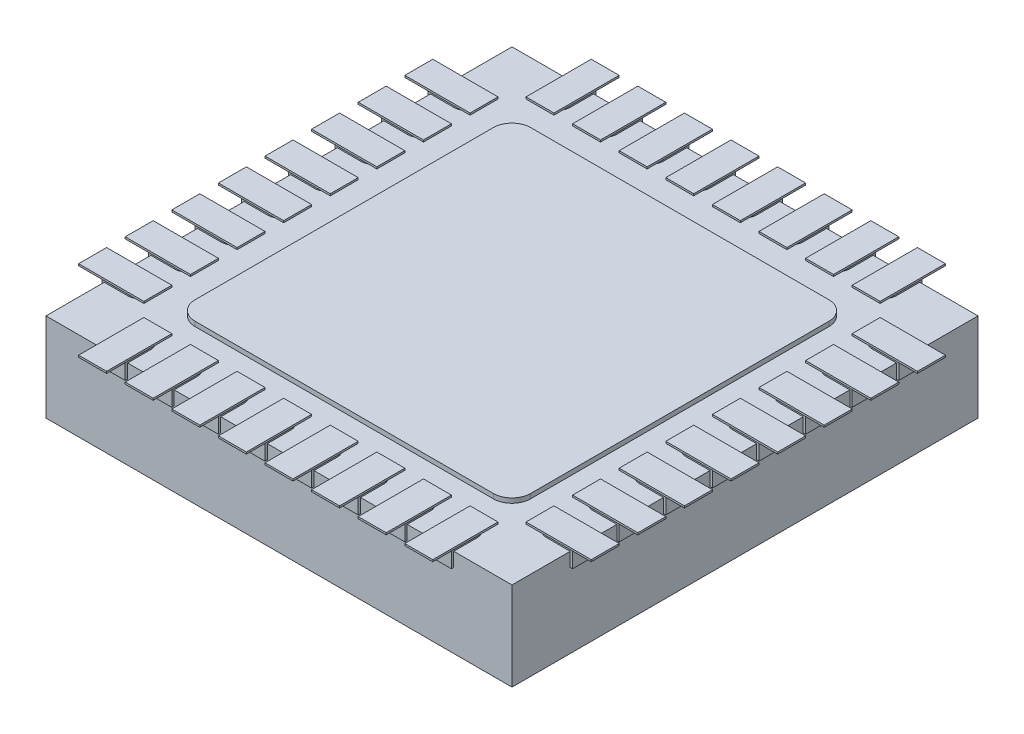
SolidWorks part; units mm, degrees
ref_plane "Front Plane" through (0, 0, 0) normal (0, 0, 1) x (1, 0, 0)
ref_plane "Top Plane" through (0, 0, 0) normal (0, 1, 0) x (1, 0, 0)
ref_plane "Right Plane" through (0, 0, 0) normal (1, 0, 0) x (0, 0, -1)
sketch "Sketch1" plane through (0, 0, 0) normal (0, 1, 0) x (1, 0, 0)
  line L0 (0, -2.75) -> (0, 2.75) construction
  line L1 (-2.525, 2.525) -> (2.525, 2.525)
  line L2 (-2.525, 2.525) -> (-2.525, -2.525)
  line L3 (-2.525, -2.525) -> (2.525, -2.525)
  line L4 (2.525, 2.525) -> (2.525, -2.525)
  line L5 (-2.75, 0) -> (2.75, 0) construction
  dimension "D1" = 5.05
  dimension "D2" = 2.525
  dimension "D3" = 2.525
sketch "Sketch2" plane through (0, 0, 0) normal (0, 1, 0) x (1, 0, 0)
  line L0 (0, -2.75) -> (0, 2.75) construction
  line L1 (-1.6, -1.8) -> (1.6, -1.8)
  line L2 (-1.8, -1.6) -> (-1.8, 1.6)
  line L3 (-1.6, 1.8) -> (1.6, 1.8)
  line L4 (1.8, -1.6) -> (1.8, 1.6)
  line L5 (-2.75, 0) -> (2.75, 0) construction
  line L6 (-1.875, -2.25) -> (-1.875, -2.525)
  line L8 (-1.875, -2.525) -> (-1.625, -2.525)
  line L9 (-1.625, -2.525) -> (-1.625, -2.25)
  line L10 (-1.875, 2.25) -> (-1.875, 2.525)
  line L12 (-1.875, 2.525) -> (-1.625, 2.525)
  line L13 (-1.625, 2.525) -> (-1.625, 2.25)
  line L14 (-1.375, -2.25) -> (-1.375, -2.525)
  line L15 (-1.125, -2.525) -> (-1.125, -2.25)
  line L16 (-1.375, -2.525) -> (-1.125, -2.525)
  line L17 (-1.125, 2.525) -> (-1.125, 2.25)
  line L18 (-1.375, 2.25) -> (-1.375, 2.525)
  line L19 (-1.375, 2.525) -> (-1.125, 2.525)
  line L20 (-0.875, -2.25) -> (-0.875, -2.525)
  line L21 (-0.625, -2.525) -> (-0.625, -2.25)
  line L22 (-0.875, -2.525) -> (-0.625, -2.525)
  line L23 (-0.625, 2.525) -> (-0.625, 2.25)
  line L24 (-0.875, 2.25) -> (-0.875, 2.525)
  line L25 (-0.875, 2.525) -> (-0.625, 2.525)
  line L26 (-0.375, -2.25) -> (-0.375, -2.525)
  line L27 (-0.125, -2.525) -> (-0.125, -2.25)
  line L28 (-0.375, -2.525) -> (-0.125, -2.525)
  line L29 (-0.125, 2.525) -> (-0.125, 2.25)
  line L30 (-0.375, 2.25) -> (-0.375, 2.525)
  line L31 (-0.375, 2.525) -> (-0.125, 2.525)
  line L32 (0.125, -2.25) -> (0.125, -2.525)
  line L33 (0.375, -2.525) -> (0.375, -2.25)
  line L34 (0.125, -2.525) -> (0.375, -2.525)
  line L35 (0.375, 2.525) -> (0.375, 2.25)
  line L36 (0.125, 2.25) -> (0.125, 2.525)
  line L37 (0.125, 2.525) -> (0.375, 2.525)
  line L38 (0.625, -2.25) -> (0.625, -2.525)
  line L39 (0.875, -2.525) -> (0.875, -2.25)
  line L40 (0.625, -2.525) -> (0.875, -2.525)
  line L41 (0.875, 2.525) -> (0.875, 2.25)
  line L42 (0.625, 2.25) -> (0.625, 2.525)
  line L43 (0.625, 2.525) -> (0.875, 2.525)
  line L44 (1.125, -2.25) -> (1.125, -2.525)
  line L45 (1.375, -2.525) -> (1.375, -2.25)
  line L46 (1.125, -2.525) -> (1.375, -2.525)
  line L47 (1.375, 2.525) -> (1.375, 2.25)
  line L48 (1.125, 2.25) -> (1.125, 2.525)
  line L49 (1.125, 2.525) -> (1.375, 2.525)
  line L50 (1.625, -2.25) -> (1.625, -2.525)
  line L51 (1.875, -2.525) -> (1.875, -2.25)
  line L52 (1.625, -2.525) -> (1.875, -2.525)
  line L53 (1.875, 2.525) -> (1.875, 2.25)
  line L54 (1.625, 2.25) -> (1.625, 2.525)
  line L55 (1.625, 2.525) -> (1.875, 2.525)
  line L56 (-2.525, -1.875) -> (-2.245, -1.875)
  line L59 (-2.245, -1.625) -> (-2.525, -1.625)
  line L60 (2.245, -1.875) -> (2.525, -1.875)
  line L62 (2.525, -1.875) -> (2.525, -1.625)
  line L63 (2.525, -1.625) -> (2.245, -1.625)
  line L64 (-2.525, -1.625) -> (-2.525, -1.875)
  line L65 (-2.245, -1.125) -> (-2.525, -1.125)
  line L66 (-2.525, -1.375) -> (-2.245, -1.375)
  line L67 (-2.525, -1.125) -> (-2.525, -1.375)
  line L68 (2.245, -1.375) -> (2.525, -1.375)
  line L69 (2.525, -1.375) -> (2.525, -1.125)
  line L70 (2.525, -1.125) -> (2.245, -1.125)
  line L71 (-2.245, -0.625) -> (-2.525, -0.625)
  line L72 (-2.525, -0.875) -> (-2.245, -0.875)
  line L73 (-2.525, -0.625) -> (-2.525, -0.875)
  line L74 (2.245, -0.875) -> (2.525, -0.875)
  line L75 (2.525, -0.875) -> (2.525, -0.625)
  line L76 (2.525, -0.625) -> (2.245, -0.625)
  line L77 (-2.245, -0.125) -> (-2.525, -0.125)
  line L78 (-2.525, -0.375) -> (-2.245, -0.375)
  line L79 (-2.525, -0.125) -> (-2.525, -0.375)
  line L80 (2.245, -0.375) -> (2.525, -0.375)
  line L81 (2.525, -0.375) -> (2.525, -0.125)
  line L82 (2.525, -0.125) -> (2.245, -0.125)
  line L83 (-2.245, 0.375) -> (-2.525, 0.375)
  line L84 (-2.525, 0.125) -> (-2.245, 0.125)
  line L85 (-2.525, 0.375) -> (-2.525, 0.125)
  line L86 (2.245, 0.125) -> (2.525, 0.125)
  line L87 (2.525, 0.125) -> (2.525, 0.375)
  line L88 (2.525, 0.375) -> (2.245, 0.375)
  line L89 (-2.245, 0.875) -> (-2.525, 0.875)
  line L90 (-2.525, 0.625) -> (-2.245, 0.625)
  line L91 (-2.525, 0.875) -> (-2.525, 0.625)
  line L92 (2.245, 0.625) -> (2.525, 0.625)
  line L93 (2.525, 0.625) -> (2.525, 0.875)
  line L94 (2.525, 0.875) -> (2.245, 0.875)
  line L95 (-2.245, 1.375) -> (-2.525, 1.375)
  line L96 (-2.525, 1.125) -> (-2.245, 1.125)
  line L97 (-2.525, 1.375) -> (-2.525, 1.125)
  line L98 (2.245, 1.125) -> (2.525, 1.125)
  line L99 (2.525, 1.125) -> (2.525, 1.375)
  line L100 (2.525, 1.375) -> (2.245, 1.375)
  line L101 (-2.245, 1.875) -> (-2.525, 1.875)
  line L102 (-2.525, 1.625) -> (-2.245, 1.625)
  line L103 (-2.525, 1.875) -> (-2.525, 1.625)
  line L104 (2.245, 1.625) -> (2.525, 1.625)
  line L105 (2.525, 1.625) -> (2.525, 1.875)
  line L106 (2.525, 1.875) -> (2.245, 1.875)
  line L107 (-2.245, -1.625) -> (-2.245, -1.125) construction
  line L108 (-2.525, 2.525) -> (-2.525, -2.525) construction
  line L109 (-2.525, 2.525) -> (2.525, 2.525) construction
  line L110 (-2.525, -2.525) -> (2.525, -2.525) construction
  line L111 (2.525, 2.525) -> (2.525, -2.525) construction
  arc A0 (1.6, 1.8) -> (1.8, 1.6) centre (1.6, 1.6) cw
  arc A1 (-1.8, 1.6) -> (-1.6, 1.8) centre (-1.6, 1.6) cw
  arc A2 (-1.6, -1.8) -> (-1.8, -1.6) centre (-1.6, -1.6) cw
  arc A3 (1.6, -1.8) -> (1.8, -1.6) centre (1.6, -1.6) ccw
  arc A4 (-1.625, -2.25) -> (-1.875, -2.25) centre (-1.75, -2.25) ccw
  arc A5 (-1.875, 2.25) -> (-1.625, 2.25) centre (-1.75, 2.25) ccw
  arc A6 (-1.125, -2.25) -> (-1.375, -2.25) centre (-1.25, -2.25) ccw
  arc A7 (-1.375, 2.25) -> (-1.125, 2.25) centre (-1.25, 2.25) ccw
  arc A8 (-0.625, -2.25) -> (-0.875, -2.25) centre (-0.75, -2.25) ccw
  arc A9 (-0.875, 2.25) -> (-0.625, 2.25) centre (-0.75, 2.25) ccw
  arc A10 (-0.125, -2.25) -> (-0.375, -2.25) centre (-0.25, -2.25) ccw
  arc A11 (-0.375, 2.25) -> (-0.125, 2.25) centre (-0.25, 2.25) ccw
  arc A12 (0.375, -2.25) -> (0.125, -2.25) centre (0.25, -2.25) ccw
  arc A13 (0.125, 2.25) -> (0.375, 2.25) centre (0.25, 2.25) ccw
  arc A14 (0.875, -2.25) -> (0.625, -2.25) centre (0.75, -2.25) ccw
  arc A15 (0.625, 2.25) -> (0.875, 2.25) centre (0.75, 2.25) ccw
  arc A16 (1.375, -2.25) -> (1.125, -2.25) centre (1.25, -2.25) ccw
  arc A17 (1.125, 2.25) -> (1.375, 2.25) centre (1.25, 2.25) ccw
  arc A18 (1.875, -2.25) -> (1.625, -2.25) centre (1.75, -2.25) ccw
  arc A19 (1.625, 2.25) -> (1.875, 2.25) centre (1.75, 2.25) ccw
  arc A20 (-2.245, -1.875) -> (-2.245, -1.625) centre (-2.245, -1.75) ccw
  arc A21 (2.245, -1.625) -> (2.245, -1.875) centre (2.245, -1.75) ccw
  arc A22 (-2.245, -1.375) -> (-2.245, -1.125) centre (-2.245, -1.25) ccw
  arc A23 (2.245, -1.125) -> (2.245, -1.375) centre (2.245, -1.25) ccw
  arc A24 (-2.245, -0.875) -> (-2.245, -0.625) centre (-2.245, -0.75) ccw
  arc A25 (2.245, -0.625) -> (2.245, -0.875) centre (2.245, -0.75) ccw
  arc A26 (-2.245, -0.375) -> (-2.245, -0.125) centre (-2.245, -0.25) ccw
  arc A27 (2.245, -0.125) -> (2.245, -0.375) centre (2.245, -0.25) ccw
  arc A28 (-2.245, 0.125) -> (-2.245, 0.375) centre (-2.245, 0.25) ccw
  arc A29 (2.245, 0.375) -> (2.245, 0.125) centre (2.245, 0.25) ccw
  arc A30 (-2.245, 0.625) -> (-2.245, 0.875) centre (-2.245, 0.75) ccw
  arc A31 (2.245, 0.875) -> (2.245, 0.625) centre (2.245, 0.75) ccw
  arc A32 (-2.245, 1.125) -> (-2.245, 1.375) centre (-2.245, 1.25) ccw
  arc A33 (2.245, 1.375) -> (2.245, 1.125) centre (2.245, 1.25) ccw
  arc A34 (-2.245, 1.625) -> (-2.245, 1.875) centre (-2.245, 1.75) ccw
  arc A35 (2.245, 1.875) -> (2.245, 1.625) centre (2.245, 1.75) ccw
  point P14 (-1.8, -1.8)
  point P17 (1.8, -1.8)
  dimension "D5" = 0.2
  dimension "D1" = 3.6
  dimension "D2" = 1.8
  dimension "D3" = 1.8
  dimension "D4" = 1.8
  dimension "D6" = 0.25
  dimension "D7" = 0.275
  dimension "D8" = 1.75
  dimension "D10" = 0.5
  dimension "D11" = 1.75
  dimension "D12" = 0.25
  dimension "D13" = 0.28
  dimension "D15" = 0.5
  dimension "D9" = 8
  dimension "D14" = 8
sketch "Sketch3" plane through (0, 0, 0) normal (0, 1, 0) x (1, 0, 0)
  line L0 (0, -2.7775) -> (0, 2.7775) construction
  line L1 (2.5, 2.5) -> (-2.5, 2.5)
  line L2 (2.5, 2.5) -> (2.5, -2.5)
  line L3 (2.5, -2.5) -> (-2.5, -2.5)
  line L4 (-2.5, 2.5) -> (-2.5, -2.5)
  line L5 (-2.7775, 0) -> (2.7775, 0) construction
  dimension "D1" = 5
  dimension "D2" = 2.5
  dimension "D3" = 2.5
  dimension "D4" = 2.5
extrude "Boss-Extrude2" add sketch "Sketch3" against normal blind 0.95
extrude "Boss-Extrude3" add sketch "Sketch2" along normal blind 0.05 and the other way blind 0.15
ref_plane "Plane1" through (0, 0.06, 0) normal (0, 1, 0) x (1, 0, 0)
sketch "Sketch4" plane through (0, 0.06, 0) normal (0, 1, 0) x (1, 0, 0)
  line L0 (-0.5555, 0) -> (0.5555, 0) construction
  line L1 (-1.9, 2.75) -> (-1.6, 2.75)
  line L2 (-1.9, 2.75) -> (-1.9, 2.05)
  line L3 (-1.9, 2.05) -> (-1.6, 2.05)
  line L4 (-1.6, 2.75) -> (-1.6, 2.05)
  line L5 (-1.9, -2.05) -> (-1.6, -2.05)
  line L6 (-1.9, -2.05) -> (-1.9, -2.75)
  line L7 (-1.9, -2.75) -> (-1.6, -2.75)
  line L8 (-1.6, -2.05) -> (-1.6, -2.75)
  line L9 (0, -0.5555) -> (0, 0.5555) construction
  line L10 (-1.4, -2.75) -> (-1.1, -2.75)
  line L11 (-1.1, -2.05) -> (-1.1, -2.75)
  line L12 (-1.4, -2.05) -> (-1.4, -2.75)
  line L13 (-1.4, -2.05) -> (-1.1, -2.05)
  line L14 (-1.4, 2.75) -> (-1.4, 2.05)
  line L15 (-1.4, 2.05) -> (-1.1, 2.05)
  line L16 (-1.1, 2.75) -> (-1.1, 2.05)
  line L17 (-1.4, 2.75) -> (-1.1, 2.75)
  line L18 (-0.9, -2.75) -> (-0.6, -2.75)
  line L19 (-0.6, -2.05) -> (-0.6, -2.75)
  line L20 (-0.9, -2.05) -> (-0.9, -2.75)
  line L21 (-0.9, -2.05) -> (-0.6, -2.05)
  line L22 (-0.9, 2.75) -> (-0.9, 2.05)
  line L23 (-0.9, 2.05) -> (-0.6, 2.05)
  line L24 (-0.6, 2.75) -> (-0.6, 2.05)
  line L25 (-0.9, 2.75) -> (-0.6, 2.75)
  line L26 (-0.4, -2.75) -> (-0.1, -2.75)
  line L27 (-0.1, -2.05) -> (-0.1, -2.75)
  line L28 (-0.4, -2.05) -> (-0.4, -2.75)
  line L29 (-0.4, -2.05) -> (-0.1, -2.05)
  line L30 (-0.4, 2.75) -> (-0.4, 2.05)
  line L31 (-0.4, 2.05) -> (-0.1, 2.05)
  line L32 (-0.1, 2.75) -> (-0.1, 2.05)
  line L33 (-0.4, 2.75) -> (-0.1, 2.75)
  line L34 (0.1, -2.75) -> (0.4, -2.75)
  line L35 (0.4, -2.05) -> (0.4, -2.75)
  line L36 (0.1, -2.05) -> (0.1, -2.75)
  line L37 (0.1, -2.05) -> (0.4, -2.05)
  line L38 (0.1, 2.75) -> (0.1, 2.05)
  line L39 (0.1, 2.05) -> (0.4, 2.05)
  line L40 (0.4, 2.75) -> (0.4, 2.05)
  line L41 (0.1, 2.75) -> (0.4, 2.75)
  line L42 (0.6, -2.75) -> (0.9, -2.75)
  line L43 (0.9, -2.05) -> (0.9, -2.75)
  line L44 (0.6, -2.05) -> (0.6, -2.75)
  line L45 (0.6, -2.05) -> (0.9, -2.05)
  line L46 (0.6, 2.75) -> (0.6, 2.05)
  line L47 (0.6, 2.05) -> (0.9, 2.05)
  line L48 (0.9, 2.75) -> (0.9, 2.05)
  line L49 (0.6, 2.75) -> (0.9, 2.75)
  line L50 (1.1, -2.75) -> (1.4, -2.75)
  line L51 (1.4, -2.05) -> (1.4, -2.75)
  line L52 (1.1, -2.05) -> (1.1, -2.75)
  line L53 (1.1, -2.05) -> (1.4, -2.05)
  line L54 (1.1, 2.75) -> (1.1, 2.05)
  line L55 (1.1, 2.05) -> (1.4, 2.05)
  line L56 (1.4, 2.75) -> (1.4, 2.05)
  line L57 (1.1, 2.75) -> (1.4, 2.75)
  line L58 (1.6, -2.75) -> (1.9, -2.75)
  line L59 (1.9, -2.05) -> (1.9, -2.75)
  line L60 (1.6, -2.05) -> (1.6, -2.75)
  line L61 (1.6, -2.05) -> (1.9, -2.05)
  line L62 (1.6, 2.75) -> (1.6, 2.05)
  line L63 (1.6, 2.05) -> (1.9, 2.05)
  line L64 (1.9, 2.75) -> (1.9, 2.05)
  line L65 (1.6, 2.75) -> (1.9, 2.75)
  line L66 (-1.9, -2.75) -> (-1.4, -2.75) construction
  line L67 (-2.75, 1.1) -> (-2.05, 1.1)
  line L68 (-2.75, 1.9) -> (-2.05, 1.9)
  line L69 (-2.75, 1.9) -> (-2.75, 1.6)
  line L70 (-2.75, 1.6) -> (-2.05, 1.6)
  line L71 (-2.05, 1.9) -> (-2.05, 1.6)
  line L72 (2.05, 1.9) -> (2.75, 1.9)
  line L73 (2.05, 1.9) -> (2.05, 1.6)
  line L74 (2.05, 1.6) -> (2.75, 1.6)
  line L75 (2.75, 1.9) -> (2.75, 1.6)
  line L76 (-2.05, 1.4) -> (-2.05, 1.1)
  line L77 (-2.75, 1.4) -> (-2.05, 1.4)
  line L78 (-2.75, 1.4) -> (-2.75, 1.1)
  line L79 (2.05, 1.4) -> (2.75, 1.4)
  line L80 (2.75, 1.4) -> (2.75, 1.1)
  line L81 (2.05, 1.1) -> (2.75, 1.1)
  line L82 (2.05, 1.4) -> (2.05, 1.1)
  line L83 (-2.75, 0.6) -> (-2.05, 0.6)
  line L84 (-2.05, 0.9) -> (-2.05, 0.6)
  line L85 (-2.75, 0.9) -> (-2.05, 0.9)
  line L86 (-2.75, 0.9) -> (-2.75, 0.6)
  line L87 (2.05, 0.9) -> (2.75, 0.9)
  line L88 (2.75, 0.9) -> (2.75, 0.6)
  line L89 (2.05, 0.6) -> (2.75, 0.6)
  line L90 (2.05, 0.9) -> (2.05, 0.6)
  line L91 (-2.75, 0.1) -> (-2.05, 0.1)
  line L92 (-2.05, 0.4) -> (-2.05, 0.1)
  line L93 (-2.75, 0.4) -> (-2.05, 0.4)
  line L94 (-2.75, 0.4) -> (-2.75, 0.1)
  line L95 (2.05, 0.4) -> (2.75, 0.4)
  line L96 (2.75, 0.4) -> (2.75, 0.1)
  line L97 (2.05, 0.1) -> (2.75, 0.1)
  line L98 (2.05, 0.4) -> (2.05, 0.1)
  line L99 (-2.75, -0.4) -> (-2.05, -0.4)
  line L100 (-2.05, -0.1) -> (-2.05, -0.4)
  line L101 (-2.75, -0.1) -> (-2.05, -0.1)
  line L102 (-2.75, -0.1) -> (-2.75, -0.4)
  line L103 (2.05, -0.1) -> (2.75, -0.1)
  line L104 (2.75, -0.1) -> (2.75, -0.4)
  line L105 (2.05, -0.4) -> (2.75, -0.4)
  line L106 (2.05, -0.1) -> (2.05, -0.4)
  line L107 (-2.75, -0.9) -> (-2.05, -0.9)
  line L108 (-2.05, -0.6) -> (-2.05, -0.9)
  line L109 (-2.75, -0.6) -> (-2.05, -0.6)
  line L110 (-2.75, -0.6) -> (-2.75, -0.9)
  line L111 (2.05, -0.6) -> (2.75, -0.6)
  line L112 (2.75, -0.6) -> (2.75, -0.9)
  line L113 (2.05, -0.9) -> (2.75, -0.9)
  line L114 (2.05, -0.6) -> (2.05, -0.9)
  line L115 (-2.75, -1.4) -> (-2.05, -1.4)
  line L116 (-2.05, -1.1) -> (-2.05, -1.4)
  line L117 (-2.75, -1.1) -> (-2.05, -1.1)
  line L118 (-2.75, -1.1) -> (-2.75, -1.4)
  line L119 (2.05, -1.1) -> (2.75, -1.1)
  line L120 (2.75, -1.1) -> (2.75, -1.4)
  line L121 (2.05, -1.4) -> (2.75, -1.4)
  line L122 (2.05, -1.1) -> (2.05, -1.4)
  line L123 (-2.75, -1.9) -> (-2.05, -1.9)
  line L124 (-2.05, -1.6) -> (-2.05, -1.9)
  line L125 (-2.75, -1.6) -> (-2.05, -1.6)
  line L126 (-2.75, -1.6) -> (-2.75, -1.9)
  line L127 (2.05, -1.6) -> (2.75, -1.6)
  line L128 (2.75, -1.6) -> (2.75, -1.9)
  line L129 (2.05, -1.9) -> (2.75, -1.9)
  line L130 (2.05, -1.6) -> (2.05, -1.9)
  line L131 (-2.75, 1.6) -> (-2.75, 1.1) construction
  dimension "D1" = 0.3
  dimension "D2" = 0.7
  dimension "D3" = 5.5
  dimension "D4" = 2.75
  dimension "D5" = 1.9
  dimension "D7" = 0.5
  dimension "D8" = 2.75
  dimension "D9" = 5.5
  dimension "D10" = 1.9
  dimension "D11" = 0.3
  dimension "D12" = 0.7
  dimension "D14" = 0.5
  dimension "D6" = 8
  dimension "D13" = 8
extrude "Boss-Extrude4" add sketch "Sketch4" against normal blind 0.02
sketch "Sketch5" plane through (0, -0.95, 0) normal (0, -1, 0) x (1, 0, 0)
  line L0 (-1.0975, -0.97) -> (-0.81, -0.97)
  line L1 (1.2, -0.925) -> (-1.0725, -0.925)
  line L2 (-0.9755, -0.75) -> (-1.0725, -0.925)
  line L3 (-0.76, -1.155) -> (-0.495, -1.155)
  line L4 (-1.2, -1.155) -> (-1, -1.155)
  line L5 (-0.76, -1.2) -> (-0.495, -1.2)
  line L6 (-0.76, -1.385) -> (-0.495, -1.385)
  line L7 (-0.76, -1.43) -> (-0.495, -1.43)
  line L8 (-1.2, -1.67) -> (0.42, -1.67)
  line L9 (-1.2, -1.88) -> (0.6956, -1.88)
  line L10 (1.2, -0.97) -> (0.8425, -1.615)
  line L11 (-0.2, -1.615) -> (0.37, -1.615)
  line L12 (0.91, -0.97) -> (0.91, -1.045)
  line L13 (-0.9755, -0.75) -> (1.2, -0.75)
  line L14 (1.2, -0.75) -> (1.2, -0.925)
  line L15 (0.91, -1.045) -> (0.965, -1.045)
  line L16 (0.965, -1.045) -> (0.86, -1.2344)
  line L17 (0.86, -1.2344) -> (0.86, -0.97)
  line L18 (-0.81, -0.97) -> (-0.81, -1.615)
  line L19 (-0.76, -0.97) -> (-0.76, -1.615)
  line L20 (-0.35, -0.97) -> (-0.35, -1.615)
  line L21 (-0.3, -0.97) -> (-0.3, -1.515)
  line L22 (-0.11, -0.97) -> (-0.11, -1.515)
  line L23 (-0.06, -0.97) -> (-0.06, -1.545)
  line L24 (0.13, -0.97) -> (0.13, -1.535)
  line L25 (0.18, -0.97) -> (0.18, -1.535)
  line L26 (0.37, -0.97) -> (0.37, -1.615)
  line L27 (0.42, -0.97) -> (0.42, -1.67)
  line L28 (0.62, -0.97) -> (0.62, -1.67)
  line L29 (0.67, -0.97) -> (0.67, -1.615)
  line L30 (0.17, -1.545) -> (0.14, -1.545)
  line L31 (-0.06, -1.545) -> (-0.08, -1.545)
  line L32 (-0.35, -1.615) -> (-0.76, -1.615)
  line L33 (-1, -1.155) -> (-1, -1.615)
  line L34 (-1.0975, -0.97) -> (-1.2, -1.155)
  line L35 (-0.48, -1.17) -> (-0.48, -1.185)
  line L36 (0.67, -1.615) -> (0.8425, -1.615)
  line L37 (0.62, -1.67) -> (0.812, -1.67)
  line L38 (-0.76, -0.97) -> (-0.35, -0.97)
  line L39 (-0.3, -0.97) -> (-0.11, -0.97)
  line L40 (-0.48, -1.4) -> (-0.48, -1.415)
  line L41 (-0.81, -1.615) -> (-1, -1.615)
  line L42 (-1.2, -1.67) -> (-1.2, -1.88)
  line L43 (0.812, -1.67) -> (0.6956, -1.88)
  line L44 (-0.06, -0.97) -> (0.13, -0.97)
  line L45 (0.18, -0.97) -> (0.37, -0.97)
  line L46 (0.42, -0.97) -> (0.62, -0.97)
  line L47 (0.67, -0.97) -> (0.86, -0.97)
  line L48 (0.91, -0.97) -> (1.2, -0.97)
  line L49 (0.5555, 0) -> (-0.5555, 0) construction
  line L50 (0, -0.5555) -> (0, 0.5555) construction
  line L51 (2.5, 2.5) -> (2.5, -2.5) construction
  line L52 (-2.5, -2.5) -> (-2.5, 2.5) construction
  arc A0 (-0.2, -1.615) -> (-0.3, -1.515) centre (-0.2, -1.515) cw
  arc A1 (-0.08, -1.545) -> (-0.11, -1.515) centre (-0.08, -1.515) cw
  arc A2 (0.17, -1.545) -> (0.18, -1.535) centre (0.17, -1.535) ccw
  arc A3 (0.13, -1.535) -> (0.14, -1.545) centre (0.14, -1.535) ccw
  arc A4 (-0.495, -1.43) -> (-0.48, -1.415) centre (-0.495, -1.415) ccw
  arc A5 (-0.48, -1.4) -> (-0.495, -1.385) centre (-0.495, -1.4) ccw
  arc A6 (-0.495, -1.2) -> (-0.48, -1.185) centre (-0.495, -1.185) ccw
  arc A7 (-0.48, -1.17) -> (-0.495, -1.155) centre (-0.495, -1.17) ccw
  dimension "D25" = 0.1
  dimension "D26" = 0.03
  dimension "D28" = 0.01
  dimension "D33" = 0.015
  dimension "D1" = 0.045
  dimension "D2" = 0.045
  dimension "D3" = 0.045
  dimension "D4" = 0.055
  dimension "D5" = 61
  dimension "D6" = 0.075
  dimension "D7" = 0.055
  dimension "D8" = 0.185
  dimension "D9" = 0.185
  dimension "D10" = 0.185
  dimension "D11" = 0.21
  dimension "D12" = 0.05
  dimension "D13" = 0.05
  dimension "D14" = 0.05
  dimension "D15" = 0.05
  dimension "D16" = 0.05
  dimension "D17" = 0.05
  dimension "D18" = 0.53
  dimension "D19" = 0.2
  dimension "D20" = 0.19
  dimension "D21" = 0.19
  dimension "D22" = 0.19
  dimension "D23" = 0.41
  dimension "D24" = 2.4
  dimension "D27" = 0.07
  dimension "D29" = 0.19
  dimension "D30" = 0.19
  dimension "D31" = 0.05
  dimension "D32" = 0.28
  dimension "D34" = 0.75
  dimension "D35" = 1.2
  dimension "D36" = 0.175
  dimension "D37" = 1.3
  dimension "D38" = 1.3
sketch "Sketch6" plane through (0, -0.95, 0) normal (0, -1, 0) x (1, 0, 0)
  line L0 (1.3, 0.1) -> (-2.5795, 0.1) construction
  line L1 (1.3, 1.9) -> (-2.5795, 1.9) construction
  line L2 (1.3, 1) -> (-2.5795, 1) construction
  line L3 (0, -0.5555) -> (0, 0.5555) construction
  line L4 (0.5555, 0) -> (-0.5555, 0) construction
  text T0 "MEGA16U2" font "SWRomnd" height 0.55
  text T1 "0928 PH" font "SWRomnd" height 0.55
  text T2 "9F3451" font "SWRomnd" height 0.55
  dimension "D1" = 1.3
  dimension "D2" = 0.1
  dimension "D3" = 0.9
  dimension "D4" = 0.9
extrude "Cut-Extrude1" cut sketch "Sketch6" against normal blind 0.05
extrude "Cut-Extrude2" cut sketch "Sketch5" against normal blind 0.05 contours L41 L18 L0 L34 L4 L33 | A7 L35 A6 L5 L19 L6 A5 L40 A4 L7 L32 L20 L38 L3 | A3 L24 L44 L23 L31 A1 L22 L39 L21 A0 L11 L26 L45 L25 A2 L30 | L14 L13 L2 L1 | L46 L27 L8 L42 L9 L43 L37 L28 | L48 L12 L15 L16 L17 L47 L29 L36 L10 region at (-0.9366, -0.95, -1.2523) region at (0.0878, -0.95, -0.8381) region at (-0.5481, -0.95, -1.2925) region at (-0.39, -0.95, -1.6921) region at (0.8588, -0.95, -1.2479) region at (0.0367, -0.95, -1.2963)
sketch "Sketch7" plane through (0, -0.95, 0) normal (0, -1, 0) x (1, 0, 0)
  line L0 (0, -0.5555) -> (0, 0.5555) construction
  line L1 (0.5555, 0) -> (-0.5555, 0) construction
  circle A0 centre (1.75, -1.75) radius 0.3
  dimension "D1" = 0.6
  dimension "D2" = 1.75
  dimension "D3" = 1.75
extrude "Cut-Extrude3" cut sketch "Sketch7" against normal blind 0.1
equation "\"D2@Sketch1\"=\"D1@Sketch1\"/2"
equation "\"D3@Sketch1\"=\"D1@Sketch1\"/2"
